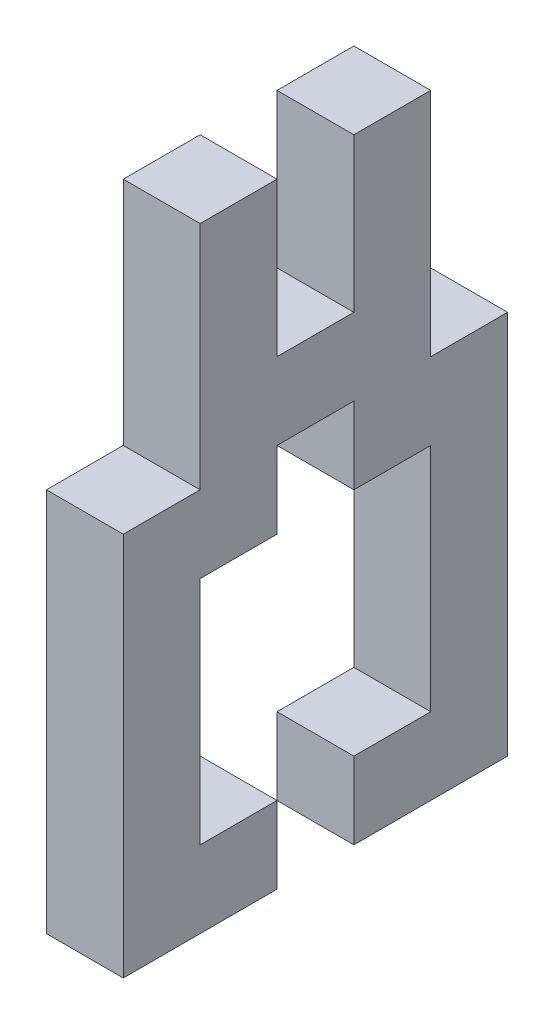
SolidWorks part; units mm, degrees
material "Pine"
ref_plane "Front Plane" through (0, 0, 0) normal (0, 0, 1) x (1, 0, 0)
ref_plane "Top Plane" through (0, 0, 0) normal (0, 1, 0) x (1, 0, 0)
ref_plane "Right Plane" through (0, 0, 0) normal (1, 0, 0) x (0, 0, -1)
sketch "Sketch2" plane through (0, 0, 0) normal (1, 0, 0) x (0, 0, -1)
  line L2 (12.7, 50.8) -> (12.7, 38.1)
  line L3 (12.7, 38.1) -> (19.05, 38.1)
  line L4 (19.05, 38.1) -> (19.05, 50.8)
  line L5 (19.05, 50.8) -> (25.4, 50.8)
  line L7 (31.75, 0) -> (0, 0)
  line L9 (6.35, 6.35) -> (25.4, 6.35)
  line L10 (6.35, 6.35) -> (6.35, 25.4)
  line L12 (25.4, 6.35) -> (25.4, 25.4)
  line L16 (25.4, 50.8) -> (25.4, 31.75)
  line L17 (25.4, 31.75) -> (31.75, 31.75)
  line L18 (31.75, 31.75) -> (31.75, 0)
  line L20 (6.35, 31.75) -> (0, 31.75)
  line L21 (0, 31.75) -> (0, 0)
  line L22 (12.7, 50.8) -> (6.35, 50.8)
  line L23 (6.35, 50.8) -> (6.35, 31.75)
  line L24 (25.4, 25.4) -> (19.05, 25.4)
  line L25 (19.05, 25.4) -> (19.05, 31.75)
  line L26 (19.05, 31.75) -> (12.7, 31.75)
  line L27 (12.7, 31.75) -> (12.7, 25.4)
  line L28 (12.7, 25.4) -> (6.35, 25.4)
  line L30 (12.7, 6.35) -> (19.05, 6.35)
  line L31 (12.7, 6.35) -> (12.7, 0)
  line L32 (12.7, 0) -> (19.05, 0)
  line L33 (19.05, 6.35) -> (19.05, 0)
  point P13 (15.875, 38.1)
  point P16 (15.875, 0)
  point P26 (15.875, 0)
  dimension "D1" = 6.35
  dimension "D2" = 19.05
  dimension "D3" = 19.05
  dimension "D4" = 6.35
  dimension "D5" = 6.35
  dimension "D6" = 6.35
  dimension "D9" = 6.35
  dimension "D10" = 6.35
  dimension "D7" = 6.35
  dimension "D8" = 6.35
  dimension "D11" = 25.4
  dimension "D12" = 6.35
  dimension "D13" = 6.35
  dimension "D14" = 6.35
extrude "Boss-Extrude1" add sketch "Sketch2" along normal blind 6.35 contours L9 L33 L7 L18 L17 L16 L5 L4 L3 L2 L22 L23 L20 L21 L31 L10 L28 L27 L26 L25 L24 L12 region at (0, 44.45, -12.1009)
equation "\"D2@Sketch2\"=\"D3@Sketch2\""
